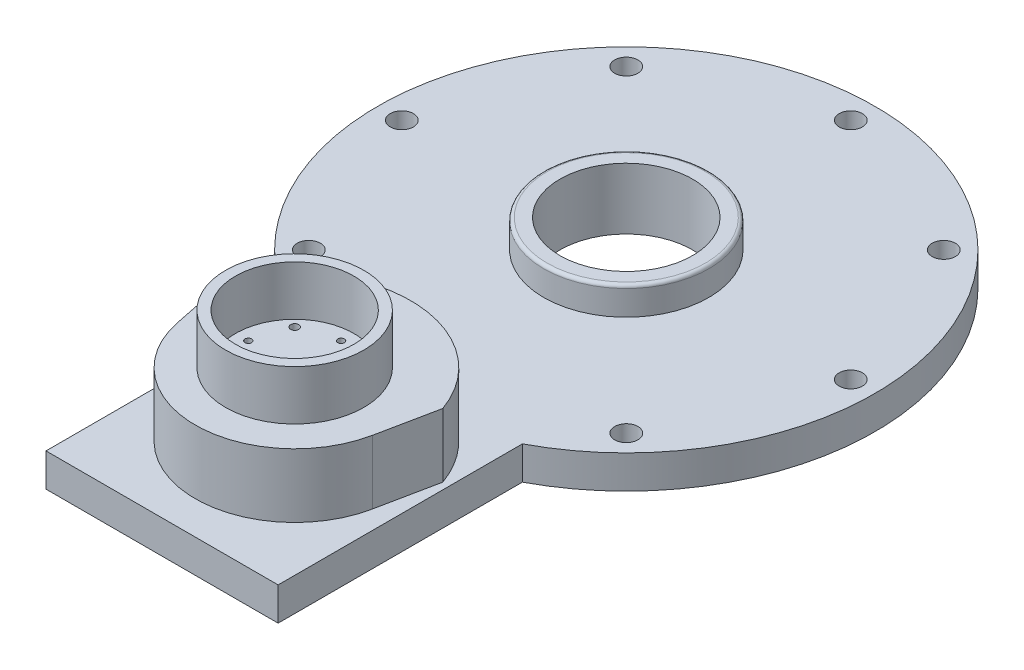
SolidWorks part; units mm, degrees
ref_plane "前视基准面" through (0, 0, 0) normal (0, 0, 1) x (1, 0, 0)
ref_plane "上视基准面" through (0, 0, 0) normal (0, 1, 0) x (1, 0, 0)
ref_plane "右视基准面" through (0, 0, 0) normal (1, 0, 0) x (0, 0, -1)
other "Configuration Table"
sketch "草图1" plane through (0, 0, 0) normal (0, 1, 0) x (1, 0, 0)
  line L0 (-57.8337, 33.3262) -> (-28.3029, -111.3445)
  line L6 (52.2485, 5.9643) -> (26.0098, -122.5784)
  circle A0 centre (0, 0) radius 50
  circle A1 centre (0, -100) radius 30
  dimension "D2" = 100
  dimension "D3" = 60
  dimension "D1" = 100
  dimension "D4" = 0
extrude "凸台-拉伸1" add sketch "草图1" along normal blind 10 contours A0 | A0 | A1 A0 | A1 region at (0, 0, 59.4922) region at (0, 0, 0) region at (0, 0, 100)
sketch "草图2" plane through (0, 10, 0) normal (0, 1, 0) x (1, 0, 0)
  circle A0 centre (0, 0) radius 24.9
  dimension "D1" = 49.8
extrude "凸台-拉伸2" add sketch "草图2" along normal blind 8.5
fillet "圆角1" radius 1 1 edges at (0, 18.5, 24.9)
sketch "草图3" plane through (0, 10, 0) normal (0, 1, 0) x (1, 0, 0)
  circle A0 centre (0, -100) radius 35
  dimension "D1" = 70
extrude "切除-拉伸1" cut sketch "草图3" against normal blind 5
sketch "草图4" plane through (0, 5, 0) normal (0, 1, 0) x (1, 0, 0)
  line L0 (-25, -75.5051) -> (0, -100)
  line L1 (0, -100) -> (25, -75.5051)
  line L6 (-32.9994, -88.3365) -> (-29.3939, -106)
  line L7 (-32.9994, -88.3365) -> (-29.3939, -106)
  line L8 (29.3939, -106) -> (32.9994, -88.3365)
  line L9 (29.3939, -106) -> (32.9994, -88.3365)
  circle A0 centre (0, -100) radius 19
  arc A3 (-29.3939, -106) -> (29.3939, -106) centre (0, -100) ccw
  arc A4 (32.9994, -88.3365) -> (-32.9994, -88.3365) centre (0, -100) ccw
  arc A5 (-29.3939, -106) -> (29.3939, -106) centre (0, -100) ccw
  arc A6 (32.9994, -88.3365) -> (-32.9994, -88.3365) centre (0, -100) ccw
  line M5 (-32.9994, -88.3365) -> (-29.3939, -106)
  arc M6 (-29.3939, -106) -> (29.3939, -106) centre (0, -100) ccw
  line M7 (29.3939, -106) -> (32.9994, -88.3365)
  arc M8 (32.9994, -88.3365) -> (-32.9994, -88.3365) centre (0, -100) ccw
  dimension "D1" = 38
  dimension "D3" = 25
  dimension "D4" = 25
  dimension "D2" = 0
extrude "凸台-拉伸4" add sketch "草图4" along normal blind 24.25 contours A0 L0 L1 M8 M5 M6 M7 region at (-19.8847, 5, 81.7153)
fillet "圆角2" radius 5 2 edges at (13.5714, 17.125, 86.7028) (-13.5714, 17.125, 86.7028)
sketch "草图5" plane through (0, 5, 0) normal (0, 1, 0) x (1, 0, 0)
  line L2 (-25, -75.5051) -> (-16.7667, -83.572)
  line L3 (16.7667, -83.572) -> (25, -75.5051)
  line L4 (-25, -75.5051) -> (-16.7667, -83.572)
  line L5 (16.7667, -83.572) -> (25, -75.5051)
  arc A4 (-16.0439, -89.8219) -> (-16.7667, -83.572) centre (-20.266, -87.1435) ccw
  arc A5 (-16.0439, -89.8219) -> (16.0439, -89.8219) centre (0, -100) ccw
  arc A6 (16.7667, -83.572) -> (16.0439, -89.8219) centre (20.266, -87.1435) ccw
  arc A7 (25, -75.5051) -> (-25, -75.5051) centre (0, -100) ccw
  arc A8 (-16.0439, -89.8219) -> (-16.7667, -83.572) centre (-20.266, -87.1435) ccw
  arc A9 (-16.0439, -89.8219) -> (16.0439, -89.8219) centre (0, -100) ccw
  arc A10 (16.7667, -83.572) -> (16.0439, -89.8219) centre (20.266, -87.1435) ccw
  arc A11 (25, -75.5051) -> (-25, -75.5051) centre (0, -100) ccw
  dimension "D1" = 0
extrude "切除-拉伸2" cut sketch "草图5" against normal through all
sketch "草图6" plane through (0, 29.25, 0) normal (0, 1, 0) x (1, 0, 0)
  line L4 (25, -75.5051) -> (16.7667, -83.572)
  line L5 (-16.7667, -83.572) -> (-25, -75.5051)
  line L6 (-32.9994, -88.3365) -> (-29.3939, -106)
  line L7 (-32.9994, -88.3365) -> (-29.3939, -106)
  line L8 (25, -75.5051) -> (16.7667, -83.572)
  line L9 (-16.7667, -83.572) -> (-25, -75.5051)
  line L12 (29.3939, -106) -> (32.9994, -88.3365)
  line L13 (29.3939, -106) -> (32.9994, -88.3365)
  circle A0 centre (0, -100) radius 35
  arc A6 (16.7667, -83.572) -> (16.0439, -89.8219) centre (20.266, -87.1435) ccw
  arc A7 (-16.0439, -89.8219) -> (16.0439, -89.8219) centre (0, -100) ccw
  arc A8 (-16.0439, -89.8219) -> (-16.7667, -83.572) centre (-20.266, -87.1435) ccw
  arc A9 (-25, -75.5051) -> (-32.9994, -88.3365) centre (0, -100) ccw
  arc A11 (-29.3939, -106) -> (29.3939, -106) centre (0, -100) ccw
  arc A12 (16.7667, -83.572) -> (16.0439, -89.8219) centre (20.266, -87.1435) ccw
  arc A13 (-16.0439, -89.8219) -> (16.0439, -89.8219) centre (0, -100) ccw
  arc A14 (-16.0439, -89.8219) -> (-16.7667, -83.572) centre (-20.266, -87.1435) ccw
  arc A15 (-25, -75.5051) -> (-32.9994, -88.3365) centre (0, -100) ccw
  arc A18 (-29.3939, -106) -> (29.3939, -106) centre (0, -100) ccw
  arc A19 (32.9994, -88.3365) -> (25, -75.5051) centre (0, -100) ccw
  arc A20 (32.9994, -88.3365) -> (25, -75.5051) centre (0, -100) ccw
  line M11 (25, -75.5051) -> (16.7667, -83.572)
  arc M12 (16.7667, -83.572) -> (16.0439, -89.8219) centre (20.266, -87.1435) ccw
  arc M13 (16.0439, -89.8219) -> (-16.0439, -89.8219) centre (0, -100) cw
  arc M14 (-16.0439, -89.8219) -> (-16.7667, -83.572) centre (-20.266, -87.1435) ccw
  line M15 (-16.7667, -83.572) -> (-25, -75.5051)
  arc M16 (-25, -75.5051) -> (-32.9994, -88.3365) centre (0, -100) ccw
  line M17 (-32.9994, -88.3365) -> (-29.3939, -106)
  arc M18 (-29.3939, -106) -> (29.3939, -106) centre (0, -100) ccw
  line M19 (29.3939, -106) -> (32.9994, -88.3365)
  arc M20 (32.9994, -88.3365) -> (25, -75.5051) centre (0, -100) ccw
  dimension "D1" = 0
extrude "凸台-拉伸6" add sketch "草图6" against normal blind 4 contours M20 M11 M12 M13 M14 M15 M16 M17 M18 M19 | A0 M11 M15 M14 M13 M12 region at (28.9746, 29.25, 81.9364) region at (0, 29.25, 90.5682)
sketch "草图7" plane through (0, 29.25, 0) normal (0, 1, 0) x (1, 0, 0)
  circle A0 centre (0, -86) radius 2.5
  circle A1 centre (-14, -100) radius 2.5
  arc A2 (-17.75, -100) -> (17.75, -100) centre (0, -100) ccw
  arc A3 (17.75, -100) -> (-17.75, -100) centre (0, -100) ccw
  circle A4 centre (0, -114) radius 2.5
  circle A5 centre (14, -100) radius 2.5
  circle A6 centre (0, -86) radius 1
  circle A7 centre (14, -100) radius 1
  circle A8 centre (0, -114) radius 1
  circle A9 centre (-14, -100) radius 1
  circle A10 centre (-10.6066, -89.3934) radius 1.25
  circle A11 centre (10.6066, -89.3934) radius 1.25
  circle A12 centre (10.6066, -110.6066) radius 1.25
  circle A13 centre (-10.6066, -110.6066) radius 1.25
extrude "切除-拉伸3" cut sketch "草图7" against normal through all contours A9 | A6 | A11 | A7 | A12 | A13 | A10 | A8 region at (0, 29.25, 86) region at (14, 29.25, 100) region at (-14, 29.25, 100) region at (10.6066, 29.25, 89.3934) region at (10.6066, 29.25, 110.6066) region at (-10.6066, 29.25, 110.6066)
sketch "草图8" plane through (0, 18.5, 0) normal (0, 1, 0) x (1, 0, 0)
  circle A0 centre (0, 0) radius 20
  dimension "D1" = 40
extrude "切除-拉伸4" cut sketch "草图8" against normal through all
sketch "草图9" plane through (0, 0, 0) normal (0, -1, 0) x (1, 0, 0)
  line L0 (-43.5496, 111.6516) -> (-72.4342, -29.8537)
  line L1 (43.1702, 113.5102) -> (70.8442, -22.0642)
  line L2 (48.9898, 10) -> (29.3939, 106)
  line L3 (-29.3939, 106) -> (-48.9898, 10)
  line L4 (48.9898, 10) -> (29.3939, 106)
  line L5 (-29.3939, 106) -> (-48.9898, 10)
  circle A0 centre (0, 0) radius 20
  circle A1 centre (0, 0) radius 65
  arc A2 (-48.9898, 10) -> (48.9898, 10) centre (0, 0) ccw
  arc A3 (29.3939, 106) -> (-29.3939, 106) centre (0, 100) ccw
  arc A4 (-48.9898, 10) -> (48.9898, 10) centre (0, 0) ccw
  arc A5 (29.3939, 106) -> (-29.3939, 106) centre (0, 100) ccw
  circle A6 centre (0, 100) radius 45
  arc M12 (-48.9898, 10) -> (48.9898, 10) centre (0, 0) ccw
  line M13 (48.9898, 10) -> (29.3939, 106)
  arc M14 (29.3939, 106) -> (-29.3939, 106) centre (0, 100) ccw
  line M15 (-29.3939, 106) -> (-48.9898, 10)
  dimension "D2" = 130
  dimension "D3" = 90
  dimension "D1" = 0
extrude "凸台-拉伸7" add sketch "草图9" against normal up to surface (10 mm away) contours L5 A1 M13 M12 | A6 L0 A1 L5 | A6 M13 M15 M14 | A6 L4 A1 L1 region at (-47.6476, 0, 61.997) region at (0, 0, 143.8483) region at (-53.9985, 0, 32.9538) region at (47.6476, 0, 61.997) up to face at (0, 10, 46.0506)
sketch "草图10" plane through (0, 0, 0) normal (0, -1, 0) x (1, 0, 0)
  line L2 (63.6867, 13) -> (44.0908, 109)
  line L3 (-44.0908, 109) -> (-63.6867, 13)
  line L4 (63.6867, 13) -> (44.0908, 109)
  line L5 (-44.0908, 109) -> (-63.6867, 13)
  arc A2 (44.0908, 109) -> (-44.0908, 109) centre (0, 100) ccw
  arc A3 (-63.6867, 13) -> (63.6867, 13) centre (0, 0) ccw
  arc A4 (44.0908, 109) -> (-44.0908, 109) centre (0, 100) ccw
  arc A5 (-63.6867, 13) -> (63.6867, 13) centre (0, 0) ccw
  dimension "D1" = 0
sketch "草图11" plane through (0, 29.25, 0) normal (0, 1, 0) x (1, 0, 0)
  circle A0 centre (0, -100) radius 20.85
  circle A1 centre (0, -100) radius 17.85
  dimension "D1" = 35.7
  dimension "D2" = 3
extrude "凸台-拉伸8" add sketch "草图11" along normal blind 15
sketch "草图12" plane through (0, 0, 0) normal (0, -1, 0) x (1, 0, 0)
  line L0 (-15.6127, 110.3548) -> (-50.7131, -1.2575)
  line L1 (12.8471, 119.1489) -> (64.1948, -44.1265)
  circle A0 centre (0, 100) radius 18
  circle A1 centre (0, 0) radius 48
  circle A2 centre (0, 100) radius 35
  line M4 (16.7667, 83.572) -> (25, 75.5051)
  line M6 (-25, 75.5051) -> (-16.7667, 83.572)
  arc M7 (-16.7667, 83.572) -> (-16.0439, 89.8219) centre (-20.266, 87.1435) ccw
  arc M8 (-16.0439, 89.8219) -> (16.0439, 89.8219) centre (0, 100) cw
  arc M9 (16.0439, 89.8219) -> (16.7667, 83.572) centre (20.266, 87.1435) ccw
  dimension "D1" = 36
  dimension "D2" = 96
extrude "切除-拉伸5" cut sketch "草图12" against normal up to surface (25.25 mm away) contours L0 A2 M6 M7 M8 | A2 L1 M4 M8 M9 region at (-20.344, 0, 86.0537) region at (20.344, 0, 86.0537) up to face at (-14, 25.25, 101)
sketch "草图13" plane through (0, 0, 0) normal (0, -1, 0) x (1, 0, 0)
  line L0 (0, 0) -> (0, 100)
  line L16 (-45, 140) -> (45, 140)
  line L17 (-45, 140) -> (-45, 40)
  line L19 (63.6867, 13) -> (44.0908, 109)
  line L20 (-44.0908, 109) -> (-63.6867, 13)
  line L21 (63.6867, 13) -> (44.0908, 109)
  line L22 (-44.0908, 109) -> (-63.6867, 13)
  line L24 (-45, 40) -> (45, 40)
  line L25 (45, 140) -> (45, 40)
  line L26 (-45, 140) -> (45, 40) construction
  line L27 (-45, 40) -> (45, 140) construction
  circle A0 centre (0, 0) radius 75
  arc A4 (44.0908, 109) -> (-44.0908, 109) centre (0, 100) ccw
  arc A5 (-63.6867, 13) -> (63.6867, 13) centre (0, 0) ccw
  arc A7 (-63.6867, 13) -> (63.6867, 13) centre (0, 0) ccw
  point P0 (0, 90)
  line M13 (63.6867, 13) -> (44.0908, 109)
  arc M14 (44.0908, 109) -> (-44.0908, 109) centre (0, 100) ccw
  line M15 (-44.0908, 109) -> (-63.6867, 13)
  arc M16 (-63.6867, 13) -> (63.6867, 13) centre (0, 0) ccw
  dimension "D2" = 150
  dimension "D1" = 90
  dimension "D3" = 0
  dimension "D4" = 0
  dimension "D5" = 10
  dimension "D6" = 100
extrude "凸台-拉伸9" add sketch "草图13" against normal up to surface (10 mm away) contours A0 M15 M14 | A0 L21 M14 | A0 M13 M16 M15 | A0 M13 | L22 A0 | L25 L16 L21 M14 region at (38.2032, 0, 130.6842) region at (68.3195, 0, 25.859) region at (-38.2032, 0, 130.6842) up to face at (0, 10, 92.2963)
sketch "草图16" plane through (0, 0, 0) normal (0, -1, 0) x (1, 0, 0)
  line L0 (0, 0) -> (0, 100)
  line L9 (-45, 140) -> (45, 140)
  line L20 (-45, 140) -> (-45, 40)
  line L21 (63.6867, 13) -> (44.0908, 109)
  line L24 (-44.0908, 109) -> (-63.6867, 13)
  line L25 (-45, 40) -> (45, 40)
  line L26 (45, 140) -> (45, 40)
  line L27 (-45, 140) -> (45, 40) construction
  line L28 (-45, 40) -> (45, 140) construction
  circle A1 centre (0, 0) radius 75
  arc A2 (-63.6867, 13) -> (63.6867, 13) centre (0, 0) ccw
  point P0 (0, 90)
  arc M10 (20.6155, 140) -> (-20.6155, 140) centre (0, 100) ccw
  line M21 (56.2034, 49.6606) -> (45, 104.5459)
  line M26 (-45, 104.5459) -> (-56.2034, 49.6606)
  dimension "D2" = 90
  dimension "D1" = 150
  dimension "D3" = 0
  dimension "D4" = 10
  dimension "D5" = 100
extrude "切除-拉伸9" cut sketch "草图16" against normal through all contours M26 | M21 | M10 region at (48.7028, 0, 71.6668) region at (-48.7028, 0, 71.6668) region at (0, 0, 142.0098)
sketch "草图17" plane through (0, 0, 0) normal (0, -1, 0) x (1, 0, 0)
  line L5 (45, 140) -> (-45, 140)
  line L25 (-45, 140) -> (-45, 60)
  line L27 (-45, 140) -> (-45, 60)
  line L32 (45, 140) -> (-45, 140)
  line L34 (45, 60) -> (45, 140)
  line L35 (45, 60) -> (45, 140)
  arc A1 (-45, 60) -> (45, 60) centre (0, 0) ccw
  arc A3 (-45, 60) -> (45, 60) centre (0, 0) ccw
  dimension "D1" = 0
sketch "草图18" plane through (0, 10, 0) normal (0, 1, 0) x (1, 0, 0)
  line L0 (45, -140) -> (45, -60)
  line L1 (-45, -60) -> (-45, -140)
  line L2 (-45, -140) -> (45, -140)
  arc A0 (45, -60) -> (-45, -60) centre (0, 0) ccw
  circle A1 centre (0, 67.7) radius 3.5
  circle A2 centre (-47.8711, 47.8711) radius 3.5
  circle A3 centre (47.8711, 47.8711) radius 3.5
  circle A4 centre (67.7, 0) radius 3.5
  circle A5 centre (47.8711, -47.8711) radius 3.5
  circle A6 centre (-67.7, 0) radius 3.5
  circle A7 centre (-47.8711, -47.8711) radius 3.5
extrude "切除-拉伸10" cut sketch "草图18" against normal through all contours A5 | A4 | A3 | A2 | A1 | A6 | A7
sketch "草图19" plane through (0, 10, 0) normal (0, 1, 0) x (1, 0, 0)
  line L3 (-45, -60) -> (-45, -140)
  line L4 (-45, -140) -> (45, -140)
  line L5 (45, -140) -> (45, -60)
  line L6 (-45, -60) -> (-45, -140)
  line L7 (-45, -140) -> (45, -140)
  line L8 (45, -140) -> (45, -60)
  line L11 (-35, -60) -> (35, -60)
  line L12 (-35, -60) -> (-35, -140)
  line L13 (-35, -140) -> (35, -140)
  line L14 (35, -60) -> (35, -140)
  line L15 (-35, -60) -> (35, -140) construction
  line L16 (-35, -140) -> (35, -60) construction
  circle A0 centre (0, 0) radius 75
  arc A1 (45, -60) -> (-45, -60) centre (0, 0) ccw
  arc A2 (45, -60) -> (-45, -60) centre (0, 0) ccw
  point P5 (0, -100)
  line M21 (-45, -60) -> (-45, -140)
  line M22 (-45, -140) -> (45, -140)
  line M23 (45, -140) -> (45, -60)
  dimension "D2" = 10
  dimension "D1" = 0
extrude "切除-拉伸11" cut sketch "草图19" against normal through all contours A0 L12 M21 M22 | A0 L14 M22 M23 region at (-40.0687, 10, 101.6537) region at (40.0687, 10, 101.6537)
